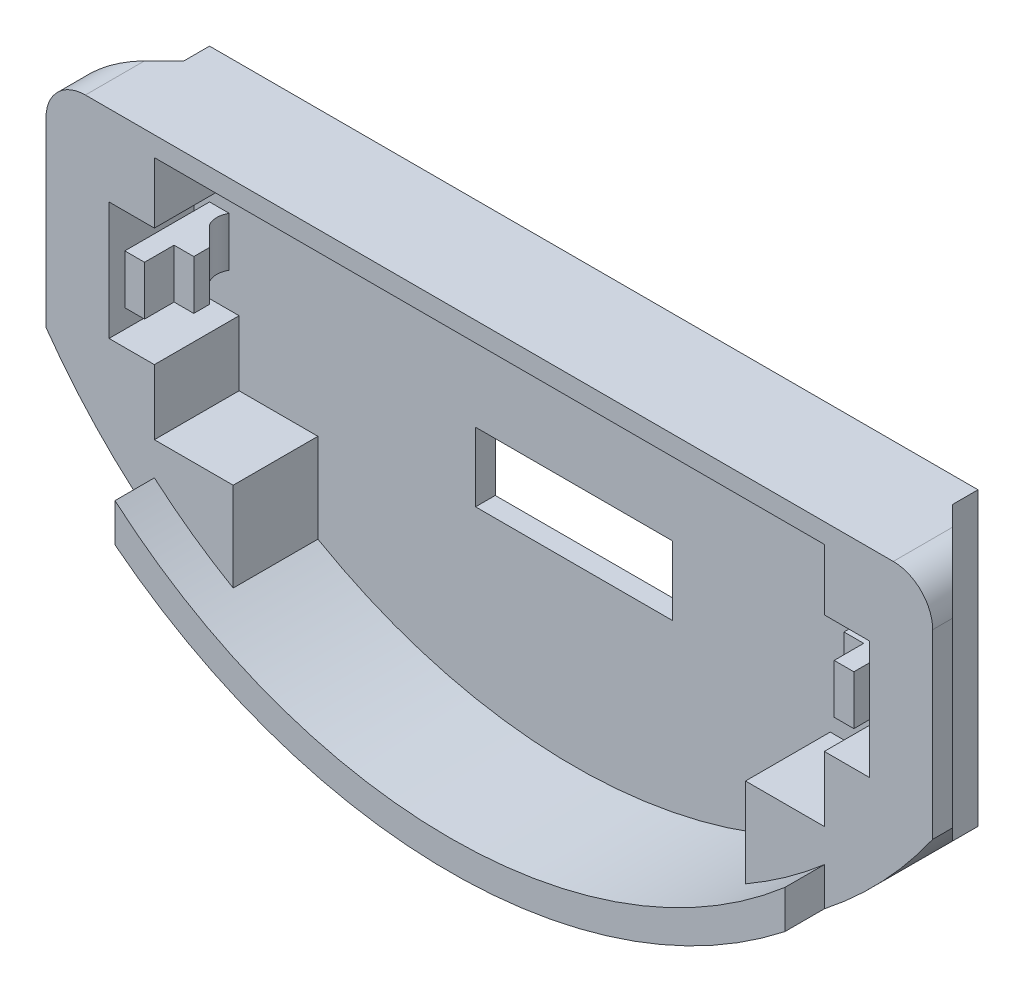
SolidWorks part; units mm, degrees
ref_plane "Front Plane" through (0, 0, 0) normal (0, 0, 1) x (1, 0, 0)
ref_plane "Top Plane" through (0, 0, 0) normal (0, 1, 0) x (1, 0, 0)
ref_plane "Right Plane" through (0, 0, 0) normal (1, 0, 0) x (0, 0, -1)
sketch "Sketch1" plane through (0, 0, 0) normal (0, 0, 1) x (-1, 0, 0)
  line L0 (-22.5, 4.1157) -> (-22.5, -5.1)
  line L2 (22.5, -5.1) -> (22.5, 4.1157)
  line L3 (-17, -6.1) -> (-17, -3)
  line L4 (-17, -6.1) -> (17, -6.1)
  line L5 (17, -6.1) -> (17, -3)
  line L6 (-20.5, -7.1) -> (20.5, -7.1)
  line L11 (-17, 6.3) -> (-13, 6.3)
  line L12 (-5, 1.9) -> (5, 1.9)
  line L13 (-5, 1.9) -> (-5, 5.4)
  line L18 (-5, 5.4) -> (5, 5.4)
  line L19 (5, 1.9) -> (5, 5.4)
  line L20 (-5, 1.9) -> (5, 5.4) construction
  line L21 (-5, 5.4) -> (5, 1.9) construction
  line L26 (-16.8, -6.1) -> (16.8, -6.1) construction
  line L27 (-16.8, -6.1) -> (-16.8, 6.1) construction
  line L28 (0, 0) -> (0, 17.0761) construction
  line L29 (-16.8, 6.1) -> (16.8, 6.1) construction
  line L30 (16.8, -6.1) -> (16.8, 6.1) construction
  line L31 (-16.8, -6.1) -> (16.8, 6.1) construction
  line L32 (-16.8, 6.1) -> (16.8, -6.1) construction
  line L33 (-13, 6.3) -> (-13, 10.821)
  line L34 (17, 6.3) -> (13, 6.3)
  line L35 (13, 6.3) -> (13, 10.821)
  line L36 (0, 0) -> (-9.1988, 0) construction
  line L37 (-17, 3) -> (-19.3, 3)
  line L39 (-17, -3) -> (-19.3, -3)
  line L40 (-19.3, 3) -> (-19.3, -3)
  line L41 (17, 3) -> (19.3, 3)
  line L43 (17, -3) -> (19.3, -3)
  line L44 (19.3, 3) -> (19.3, -3)
  line L45 (-17, 3) -> (-17, 6.3)
  line L46 (17, 3) -> (17, 6.3)
  line L48 (-17.5, 1.25) -> (-18.5, 1.25)
  line L49 (-17.5, 1.25) -> (-17.5, -1.25)
  line L50 (-17.5, -1.25) -> (-18.5, -1.25)
  line L51 (-18.5, 1.25) -> (-18.5, -1.25)
  line L52 (17.5, 1.25) -> (18.5, 1.25)
  line L53 (17.5, 1.25) -> (17.5, -1.25)
  line L54 (17.5, -1.25) -> (18.5, -1.25)
  line L55 (18.5, 1.25) -> (18.5, -1.25)
  arc A1 (-13, 10.821) -> (13, 10.821) centre (0, -11.6956) cw
  arc A2 (-22.5, 4.1157) -> (22.5, 4.1157) centre (0, -11.6956) cw
  arc A3 (20.5, -7.1) -> (22.5, -5.1) centre (20.5, -5.1) ccw
  arc A6 (-20.5, -7.1) -> (-22.5, -5.1) centre (-20.5, -5.1) cw
  point P2 (0, 0)
  point P3 (0, 3.65)
  dimension "D3" = 1.5
  dimension "D13" = 2
  dimension "D14" = 26
  dimension "D15" = 11.6956
  dimension "D2" = 6.1
  dimension "D4" = 1
  dimension "D5" = 11.5
  dimension "D6" = 3.5
  dimension "D7" = 10
  dimension "D8" = 33.6
  dimension "D9" = 12.2
  dimension "D10" = 0.7
  dimension "D11" = 45
  dimension "D12" = 0.2
  dimension "D16" = 0.2
  dimension "D17" = 26
  dimension "D18" = 6
  dimension "D19" = 2.3
  dimension "D20" = 2.5
  dimension "D21" = 1
  dimension "D22" = 0.5
extrude "Boss-Extrude1" add sketch "Sketch1" against normal blind 1 contours A6 L6 A3 L2 A2 L0 L33 A1 L35 L34 L46 L41 L44 L43 L5 L4 L3 L39 L40 L37 L45 L11 | L55 L52 L53 L54 | A1 L33 L11 L45 L37 L40 L39 L3 L4 L5 L43 L44 L41 L46 L34 L35 L51 L48 L49 L50 L19 L12 L13 L18 L52 L55 L54 L53 | L48 L51 L50 L49 region at (0, -15.2994, 0) region at (16.5634, 4.55, 0) region at (18, 0, 0) region at (-18, 0, 0)
extrude "Boss-Extrude2" add sketch "Sketch1<3>" along normal blind 4.3 contours A6 L6 A3 L2 A2 L0 L33 A1 L35 L34 L46 L41 L44 L43 L5 L4 L3 L39 L40 L37 L45 L11 | L55 L52 L53 L54 | L49 L48 L51 L50 region at (0, -15.2994, 0) region at (-18, 0, 0)
sketch "Sketch1<3>" plane through (0, 0, 0) normal (0, 0, 1) x (-1, 0, 0) same geometry as "Sketch1"
sketch "Sketch3" plane through (0, -1.25, 0) normal (0, -1, 0) x (1, 0, 0)
  line L0 (-17.5, 2) -> (-17.5, 1)
  line L1 (-17.5, 4.3) -> (-17.5, 0) construction
  line L2 (-17.5, 1) -> (-16.5, 2)
  line L3 (-16.5, 2) -> (-17.5, 2)
  line L5 (17.5, 1) -> (16.5, 2)
  line L8 (-17.5, 1) -> (-17.5, 0)
  line L10 (0, 0) -> (0, 8.8369) construction
  line L11 (17.5, 2) -> (17.5, 1)
  line L12 (-16.5, 2) -> (-17.5, 2)
  line L13 (-16.5, 2) -> (-16.5, 2.8)
  line L14 (-16.5, 2.8) -> (-17.5, 2.8)
  line L15 (-17.5, 2) -> (-17.5, 2.8)
  line L16 (16.5, 2) -> (17.5, 2)
  line L17 (16.5, 2.8) -> (17.5, 2.8)
  line L18 (17.5, 2) -> (17.5, 2.8)
  line L23 (16.5, 2) -> (17.5, 2)
  line L24 (16.5, 2) -> (16.5, 2.8)
  line L25 (17.5, 1) -> (17.5, 0)
  arc A0 (-17.5, 1) -> (-17.5, 0) centre (-16.634, 0.5) ccw
  arc A2 (17.5, 1) -> (17.5, 0) centre (16.634, 0.5) cw
  line M9 (-17.5, 0) -> (-17.5, 4.3)
  dimension "D4" = 1
  dimension "D1" = 1
  dimension "D2" = 1
  dimension "D3" = 1
  dimension "D5" = 0.8
extrude "Cut-Extrude1" cut sketch "Sketch3" against normal up to next contours A0 M9 | L25 A2 region at (-17.5539, -1.25, 0.5)
sketch "Sketch4" plane through (0, 7.1, 0) normal (0, 1, 0) x (1, 0, 0)
  line L0 (19.5, 1) -> (19.5, -0.3)
  line L1 (19.5, 1) -> (22.5, 1)
  line L2 (22.5, 1) -> (22.5, -3.3)
  line L3 (20.5, 1) -> (-20.5, 1) construction
  line L4 (22.5, 1) -> (22.5, -4.3) construction
  line L5 (19.5, -0.3) -> (22.5, -3.3)
  line L9 (20.5, -4.3) -> (-20.5, -4.3) construction
  line L10 (0, 0) -> (0, 14.5506) construction
  line L11 (-19.5, -0.3) -> (-22.5, -3.3)
  line L12 (-22.5, 1) -> (-22.5, -3.3)
  line L13 (-19.5, 1) -> (-22.5, 1)
  line L14 (-19.5, 1) -> (-19.5, -0.3)
  dimension "D1" = 45
  dimension "D2" = 1
  dimension "D3" = 3
extrude "Cut-Extrude2" cut sketch "Sketch4" against normal through all
sketch "Sketch5" plane through (0, 0, 4.3) normal (0, 0, 1) x (1, 0, 0)
  line L0 (17, -7.9767) -> (17, -9.9203)
  line L1 (-17, -9.9203) -> (-17, -7.9767)
  line L2 (0, 5.3141) -> (0, -21.8072) construction
  arc A0 (-17, -9.9203) -> (17, -9.9203) centre (0, 11.6956) ccw
  arc A1 (-22.5, -4.1157) -> (22.5, -4.1157) centre (0, 11.6956) ccw construction
  arc A2 (-17, -7.9767) -> (17, -7.9767) centre (0, 11.6956) ccw
  arc A3 (-13, -10.821) -> (13, -10.821) centre (0, 11.6956) ccw construction
  arc A4 (-13, -10.821) -> (13, -10.821) centre (0, 11.6956) ccw construction
  dimension "D1" = 34
extrude "Boss-Extrude4" add sketch "Sketch5" along normal blind 2
extrude "Boss-Extrude5" add sketch "Sketch3<5>" against normal up to surface (2.5 mm away) contours L24 L16 L18 L17 | L16 L5 L11 | L13 L14 L3 M9 | L2 L3 M9 region at (-17.1667, -1.25, 1.6667) region at (-17, -1.25, 2.4) region at (17.1667, -1.25, 1.6667) region at (17, -1.25, 2.4) up to face at (-17.9268, 1.25, 1.92)
sketch "Sketch3<5>" plane through (0, -1.25, 0) normal (0, -1, 0) x (1, 0, 0) same geometry as "Sketch3"
